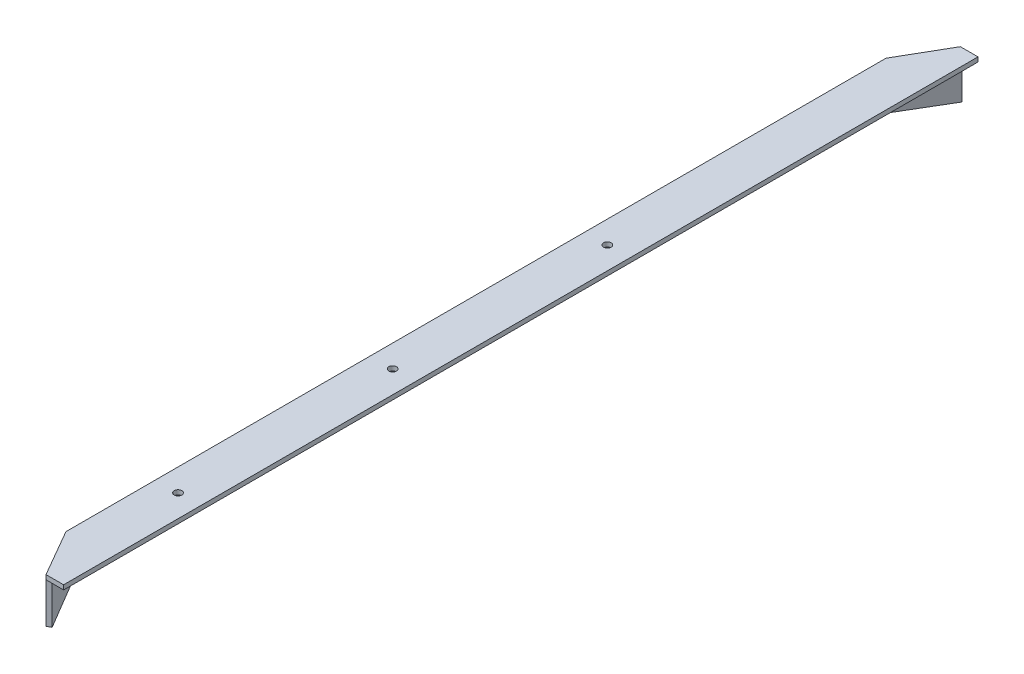
SolidWorks part; units mm, degrees
material "1.0116 (S235J2G3)"
ref_plane "Front Plane" through (0, 0, 0) normal (0, 0, 1) x (1, 0, 0)
ref_plane "Top Plane" through (0, 0, 0) normal (0, 1, 0) x (1, 0, 0)
ref_plane "Right Plane" through (0, 0, 0) normal (1, 0, 0) x (0, 0, -1)
sketch "Sketch1" plane through (0, 0, 0) normal (0, 0, 1) x (1, 0, 0)
  line L6 (0, 0) -> (0, 70)
  line L7 (0, 70) -> (70, 70)
  line L8 (70, 70) -> (70, 63)
  line L9 (70, 63) -> (7, 63)
  line L10 (7, 63) -> (7, 0)
  line L11 (7, 0) -> (0, 0)
  dimension "D1" = 70
  dimension "D2" = 70
  dimension "D3" = 7
  dimension "D4" = 7
extrude "Boss-Extrude1" add sketch "Sketch1" along normal blind 640
sketch "Sketch21" plane through (0, 0, 0) normal (0, 0, -1) x (-1, 0, 0)
  line L0 (0, 70) -> (-70, 70) construction
  line L1 (-70, 70) -> (-70, 0) construction
  line L2 (-70, 0) -> (0, 0) construction
  line L3 (0, 0) -> (0, 69.2595) construction
sketch "Sketch23" plane through (0, 0, 0) normal (0, 1, 0) x (1, 0, 0)
  line L0 (0, -640) -> (42.5, -713.6122)
  line L1 (42.5, -713.6122) -> (48.5622, -710.1122)
  line L2 (48.5622, -710.1122) -> (7, -640)
  line L3 (7, -640) -> (0, -640)
  line L4 (0, -38.5) -> (0, 38.5) construction
  dimension "D1" = 7
  dimension "D2" = 210
  dimension "D3" = 85
extrude "Boss-Extrude2" add sketch "Sketch23" along normal blind 63
sketch "Sketch25" plane through (0, 63, 0) normal (0, 1, 0) x (1, 0, 0)
  line L0 (70, -640) -> (0, -640)
  line L1 (70, -640) -> (70, 0) construction
  line L2 (7, -640) -> (70, -640) construction
  line L3 (0, -640) -> (42.5, -713.6122) construction
  line L4 (0, -640) -> (42.5, -713.6122)
  line L5 (42.5, -713.6122) -> (48.5622, -710.1122) construction
  line L6 (42.5, -713.6122) -> (70, -713.6122)
  line L7 (70, -713.6122) -> (70, -640)
extrude "Boss-Extrude3" add sketch "Sketch25" along normal blind 7
mirror "Mirror1" about plane through (0, 0, 0) normal (0, 0, 1) of bodies 113 116
sketch "Sketch28" plane through (0, 70, 0) normal (0, 1, 0) x (1, 0, 0)
  line L0 (70, -713.6122) -> (70, 713.6122) construction
  circle A0 centre (35, -500) radius 6
  circle A1 centre (35, -165) radius 6
  circle A2 centre (35, 170) radius 6
  dimension "D1" = 12
  dimension "D2" = 12
  dimension "D3" = 12
  dimension "D4" = 335
  dimension "D5" = 335
  dimension "D6" = 500
  dimension "D7" = 35
  dimension "D8" = 35
  dimension "D9" = 35
extrude "Cut-Extrude1" cut sketch "Sketch28" against normal blind 10 and the other way blind 10
